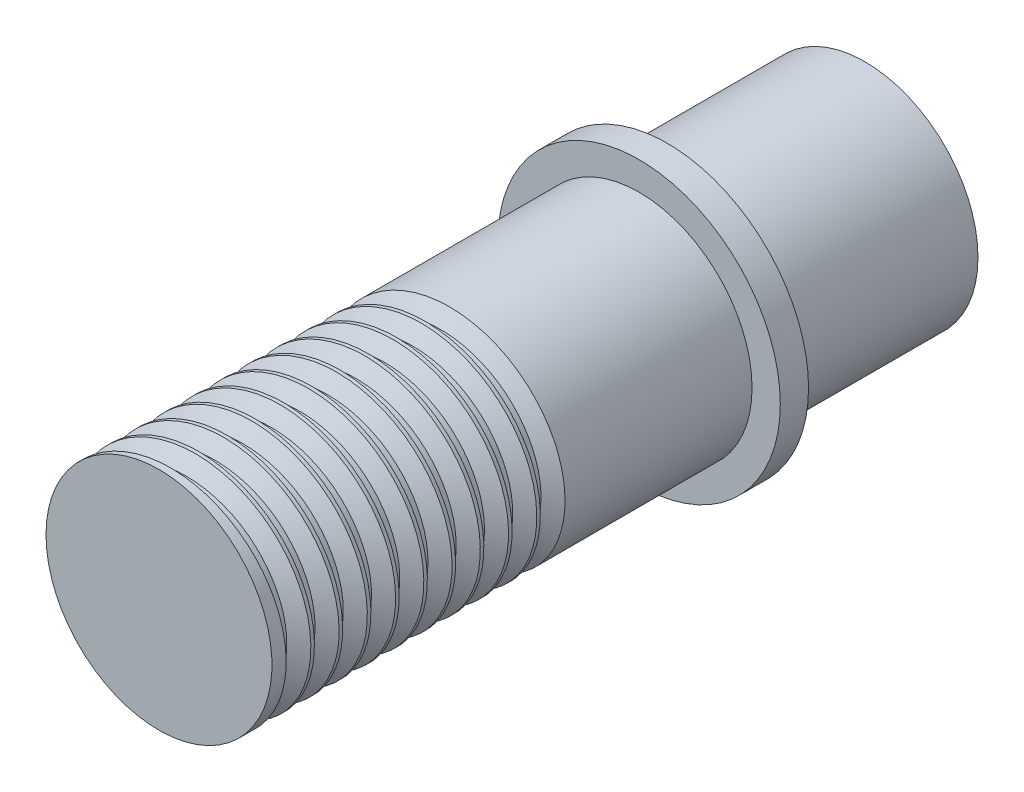
SolidWorks part; units mm, degrees
ref_plane "Front Plane" through (0, 0, 0) normal (0, 0, 1) x (1, 0, 0)
ref_plane "Top Plane" through (0, 0, 0) normal (0, 1, 0) x (1, 0, 0)
ref_plane "Right Plane" through (0, 0, 0) normal (1, 0, 0) x (0, 0, -1)
sketch "Sketch1" plane through (0, 0, 0) normal (0, 0, 1) x (1, 0, 0)
  circle A0 centre (0, 0) radius 4
  dimension "D1" = 8
extrude "Boss-Extrude1" add sketch "Sketch1" along normal blind 25
ref_plane "Plane1" through (0, 0, 7) normal (0, 0, 1) x (1, 0, 0)
sketch "Sketch2" plane through (0, 0, 7) normal (0, 0, 1) x (1, 0, 0)
  circle A0 centre (0, 0) radius 4
  circle A1 centre (0, 0) radius 5
  circle A2 centre (0, 0) radius 4 construction
  dimension "D1" = 10
extrude "Boss-Extrude2" add sketch "Sketch2" along normal blind 1
thread "Thread1" pitch 1 method cut profile "Thread Profile1" start angle 0, offset 0, length 10, pitch 1, diameter 8
ref_plane "Plane2" through (-4, 0, 25) normal (0, -1, 0) x (-1, 0, 0)
sketch "Thread Profile1" plane through (-4, 0, 25) normal (0, -1, 0) x (-1, 0, 0)
  line L0 (0, 0) -> (0, 1) construction
  line L11 (0, 0) -> (0, 0.875)
  line L12 (0, 0.875) -> (-0.5413, 0.5625)
  line L13 (-0.5413, 0.5625) -> (-0.5413, 0.3125)
  line L15 (-0.5413, 0.3125) -> (0, 0)
  line L17 (-0.5413, 0.4375) -> (0, 0.4375) construction
  point P2 (0, 0)
  dimension "Pitch" = 1
  dimension "Profile_Angle" = 60
  dimension "Profile_Land" = 0.25
  dimension "Profile_Height" = 0.5413
